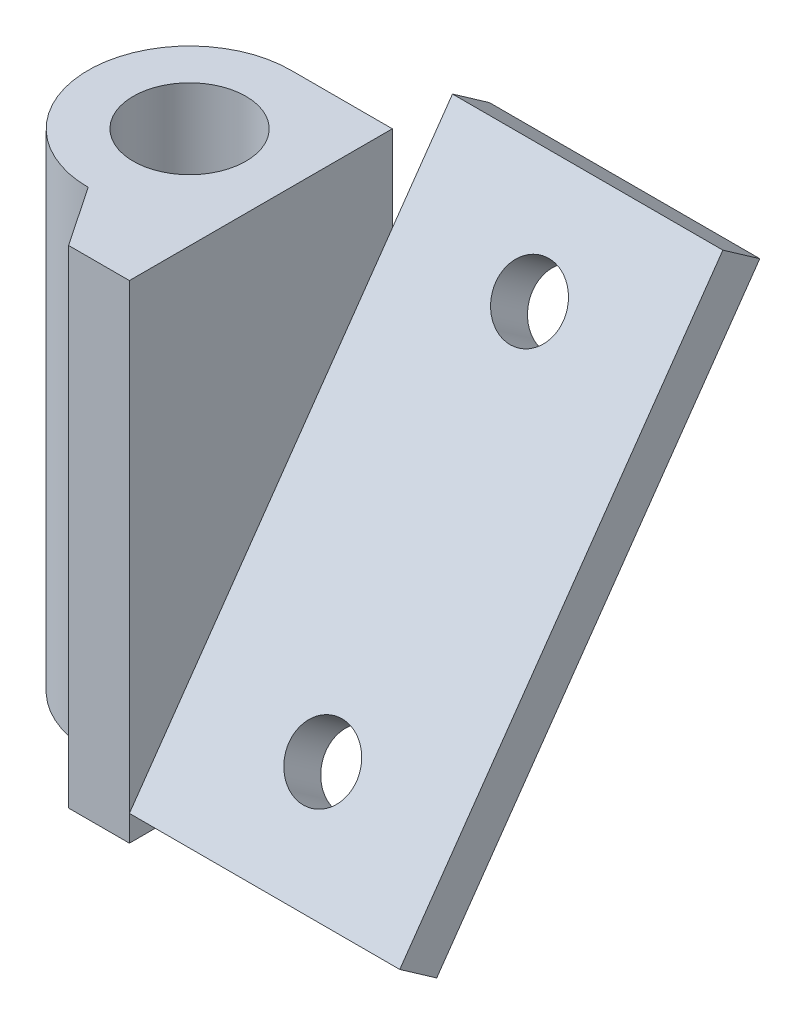
SolidWorks part; units mm, degrees
ref_plane "Alzado" through (0, 0, 0) normal (0, 0, 1) x (1, 0, 0)
ref_plane "Planta" through (0, 0, 0) normal (0, 1, 0) x (1, 0, 0)
ref_plane "Vista lateral" through (0, 0, 0) normal (1, 0, 0) x (0, 0, -1)
sketch "Croquis1" plane through (0, 0, 0) normal (0, 1, 0) x (1, 0, 0)
  line L0 (0, -4.5) -> (4.5, -4.5)
  line L1 (4.5, -4.5) -> (4.5, 0)
  line L2 (4.5, 0) -> (4.5, 4.5)
  line L3 (4.5, 4.5) -> (0, 4.5)
  circle A0 centre (0, 0) radius 2.5
  arc A1 (0, 4.5) -> (0, -4.5) centre (0, 0) ccw
  dimension "D1" = 5
  dimension "D2" = 9
extrude "Saliente-Extruir1" add sketch "Croquis1" along normal blind 10
sketch "Croquis2" plane through (4.5, 0, 0) normal (1, 0, 0) x (0, 0, -1)
  line L0 (-4.5, 0) -> (4.5, 12.8533) construction
  line L1 (4.5, 10) -> (4.5, 0) construction
  line L2 (-4.5, 10) -> (-4.5, 0) construction
  line L3 (4.5, 12.8533) -> (-4.5, 12.8533) construction
  line L4 (-4.5, 0) -> (-4.5, 1.7434)
  line L5 (-4.5, 1.7434) -> (4.5, 14.5968)
  line L6 (4.5, 14.5968) -> (4.5, 11.1099)
  line L7 (4.5, 11.1099) -> (-3.2792, 0)
  line L8 (-4.5, 0) -> (4.5, 0) construction
  line L9 (-3.2792, 0) -> (-4.5, 0)
  point P8 (0.6104, 5.5549)
  dimension "D1" = 55
  dimension "D2" = 2
  dimension "D3" = 1
extrude "Saliente-Extruir2" add sketch "Croquis2" along normal blind 12
sketch "Croquis3" plane through (0, 2.6879, 3.8387) normal (0, 0.5736, 0.8192) x (1, 0, 0)
  line L0 (10.5, 14.5381) -> (10.5, 14.6926) construction
  line L1 (16.5, 14.5381) -> (4.5, 14.5381) construction
  line L2 (10.5, 14.6926) -> (10.5, -1.3074) construction
  line L3 (10.5, -1.3074) -> (10.5, -1.1529) construction
  line L4 (16.5, -1.1529) -> (4.5, -1.1529) construction
  line L5 (4.5, 5.6104) -> (4.5, -1.1529) construction
  line L6 (4.5, 19.1926) -> (16.5, 19.1926)
  line L7 (4.5, 19.1926) -> (4.5, -5.8074)
  line L8 (4.5, -5.8074) -> (16.5, -5.8074)
  line L9 (16.5, 19.1926) -> (16.5, -5.8074)
  line L10 (16.5, 14.5381) -> (16.5, -1.1529) construction
  line L11 (16.5, 6.6926) -> (10.5, 6.6926) construction
  circle A0 centre (10.5, 14.6926) radius 1.5
  circle A1 centre (10.5, -1.3074) radius 1.5
  point P12 (10.5, 14.5381)
  point P21 (11.5, 1.9992)
  dimension "D1" = 3
  dimension "D2" = 16
  dimension "D3" = 25
extrude "Saliente-Extruir3" add sketch "Croquis3" against normal blind 2
fillet "Redondeo1" radius 2 1 edges at (4.5, 5, -0.2218)
sketch "Croquis4" plane through (0, 2.6879, 3.8387) normal (0, 0.5736, 0.8192) x (1, 0, 0)
  circle A0 centre (10.5, 14.6926) radius 1.5
  circle A1 centre (10.5, -1.3074) radius 1.5
  circle A2 centre (10.5, 14.6926) radius 1.5 construction
extrude "Cortar-Extruir1" cut sketch "Croquis4" against normal blind 6
sketch "Croquis6" plane through (0, 0, 0) normal (0, -1, 0) x (1, 0, 0)
  line L0 (4.5, -4.5) -> (0, -4.5) construction
  line L1 (0, 4.5) -> (4.5, 4.5) construction
  line L2 (4.5, -4.5) -> (0, -4.5)
  line L3 (0, 4.5) -> (4.5, 4.5)
  line L4 (4.5, -4.5) -> (4.5, 4.5)
  arc A0 (0, 4.5) -> (0, -4.5) centre (0, 0) ccw construction
  arc A1 (0, 4.5) -> (0, -4.5) centre (0, 0) ccw
  circle A2 centre (0, 0) radius 2.5 construction
  circle A3 centre (0, 0) radius 2.5
extrude "Saliente-Extruir4" add sketch "Croquis6" along normal up to vertex (3.2164 mm away) and the other way up to vertex (18.4095 mm away) up to point (4.5, -3.2164, 5.5314) other way up to point (4.5, 18.4095, -7.1697)
sketch "Croquis7" plane through (0, 18.4095, 0) normal (0, 1, 0) x (1, 0, 0)
  line L0 (0, -4.5) -> (1.8007, -7.1697)
  line L1 (1.8007, -7.1697) -> (4.5, -7.1697)
  line L2 (4.5, -7.1697) -> (4.5, -4.5)
  line L3 (4.5, -7.1697) -> (16.5, -7.1697) construction
  line L4 (4.5, -4.5) -> (0, -4.5) construction
  line L5 (4.5, -4.5) -> (0, -4.5)
  dimension "D1" = 56
extrude "Saliente-Extruir5" add sketch "Croquis7" against normal up to surface (21.626 mm away) up to face at (1.125, -3.2164, 0)
